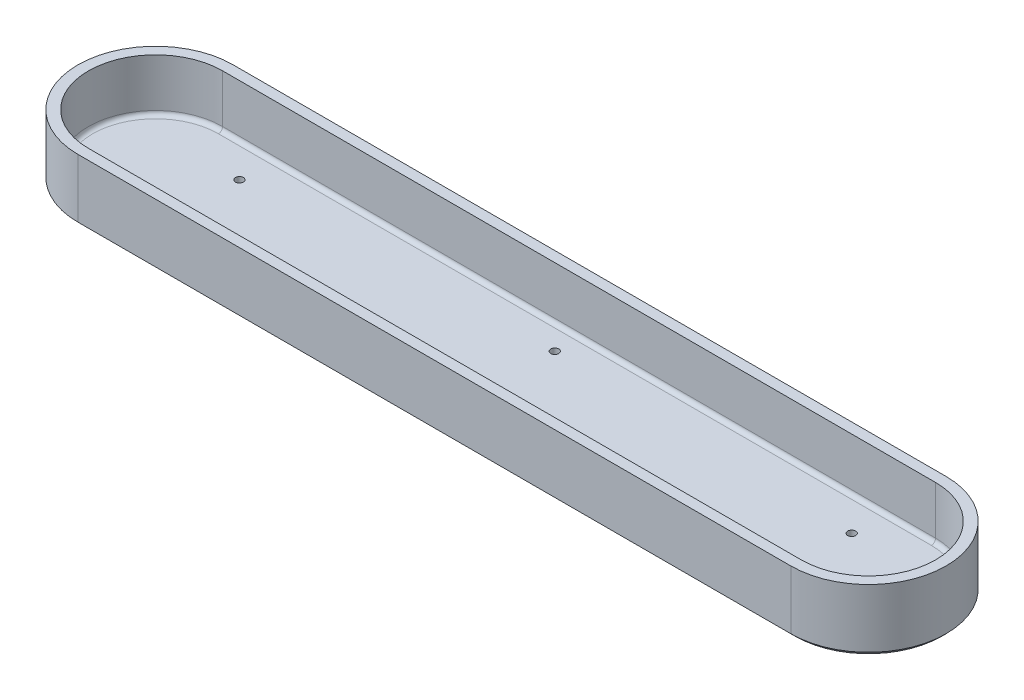
SolidWorks part; units mm, degrees
ref_plane "Front Plane" through (0, 0, 0) normal (0, 0, 1) x (1, 0, 0)
ref_plane "Top Plane" through (0, 0, 0) normal (0, 1, 0) x (1, 0, 0)
ref_plane "Right Plane" through (0, 0, 0) normal (1, 0, 0) x (0, 0, -1)
sketch "Sketch1" plane through (0, 0, 0) normal (0, 1, 0) x (1, 0, 0)
  line L0 (-107.95, 0) -> (107.95, 0) construction
  line L1 (0, -55.9739) -> (0, 55.9739) construction
  line L2 (-107.95, 20.32) -> (107.95, 20.32)
  line L3 (-107.95, -20.32) -> (107.95, -20.32)
  arc A0 (-107.95, 20.32) -> (-107.95, -20.32) centre (-107.95, 0) ccw
  arc A1 (107.95, 20.32) -> (107.95, -20.32) centre (107.95, 0) cw
  point P4 (0, 0)
  point P10 (0, 0)
  dimension "D2" = 40.64
  dimension "D1" = 215.9
extrude "MainBlock" add sketch "Sketch1" along normal blind 3.175
sketch "Sketch2" plane through (0, 0, 0) normal (0, -1, 0) x (1, 0, 0)
  line L0 (0, 0) -> (0, 50000) construction
  line L1 (-107.95, 23.495) -> (107.95, 23.495)
  line L2 (-107.95, -20.32) -> (107.95, -20.32)
  line L3 (107.95, 20.32) -> (-107.95, 20.32)
  line L5 (107.95, 20.32) -> (-107.95, 20.32)
  line L6 (-95.25, 0) -> (49904.75, 0) construction
  line L7 (107.95, -20.32) -> (-107.95, -20.32)
  line L8 (-107.95, -23.495) -> (107.95, -23.495)
  arc A0 (-107.95, 23.495) -> (-107.95, -23.495) centre (-107.95, 0) ccw
  arc A1 (107.95, 20.32) -> (107.95, -20.32) centre (107.95, 0) cw
  arc A2 (-107.95, 20.32) -> (-107.95, -20.32) centre (-107.95, 0) ccw
  arc A3 (107.95, -20.32) -> (107.95, 20.32) centre (107.95, 0) ccw
  arc A4 (-107.95, 20.32) -> (-107.95, -20.32) centre (-107.95, 0) ccw
  arc A6 (107.95, 23.495) -> (107.95, -23.495) centre (107.95, 0) cw
  point P0 (0, 20.32)
  point P15 (0, 23.495)
  point P16 (0, -20.32)
  point P19 (0, -23.495)
  dimension "2.1" = 46.99
  dimension "D1" = 0
extrude "Boss-Extrude1" add sketch "Sketch2" against normal blind 19.05
sketch "Sketch3" plane through (0, 0, 0) normal (0, -1, 0) x (1, 0, 0)
  line L0 (0, 0) -> (50000, 0) construction
  line L1 (0, 0) -> (0, 50000) construction
  line L2 (-107.95, 0.9216) -> (-107.95, 50000.9216) construction
  arc A0 (-107.95, 23.495) -> (-107.95, -23.495) centre (-107.95, 0) ccw construction
  arc A1 (-107.95, 23.495) -> (-107.95, -23.495) centre (-107.95, 0) ccw construction
  circle A2 centre (0, 12.954) radius 1.2065
  circle A3 centre (-92.71, 10.16) radius 1.2065
  circle A4 centre (92.71, 10.16) radius 1.2065
  circle A5 centre (92.71, -10.16) radius 1.2065
  circle A6 centre (-92.71, -10.16) radius 1.2065
  circle A7 centre (0, -12.954) radius 1.2065
  dimension "D1" = 2.413
  dimension "D4" = 2.413
  dimension "D2" = 12.954
  dimension "D3" = 10.16
  dimension "D5" = 15.24
extrude "Cut-Extrude1" cut sketch "Sketch3" against normal through all
fillet "Fillet1" radius 1.27 4 edges at (128.27, 3.175, 0) (0, 3.175, 20.32) (-128.27, 3.175, 0) (0, 3.175, -20.32)
chamfer "Chamfer1" distance 1.27 angle 45 4 edges at (0, 0, 23.495) (-131.445, 0, 0) (131.445, 0, 0) (0, 0, -23.495)
equation "\"D4@Sketch3\"=\"D1@Sketch3\""
